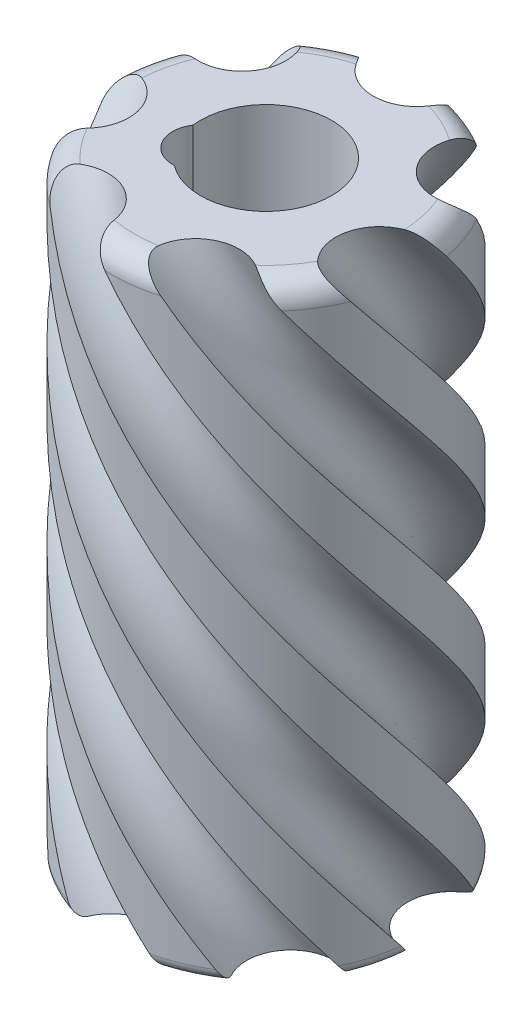
SolidWorks part; units mm, degrees
note: '?' marks a value the reader was unsure of.
ref_plane "Front Plane" through (0, 0, 0) normal (0, 0, 1) x (1, 0, 0)
ref_plane "Top Plane" through (0, 0, 0) normal (0, 1, 0) x (1, 0, 0)
ref_plane "Right Plane" through (0, 0, 0) normal (1, 0, 0) x (0, 0, -1)
sketch "Sketch4" plane through (0, 0, 0) normal (0, 1, 0) x (1, 0, 0)
  circle A0 centre (0, 0) radius 6.625
  dimension "D1" = 13.25
extrude "Boss-Extrude3" add sketch "Sketch4" along normal blind 26
sketch "Sketch2" plane through (0, 0, 0) normal (0, 1, 0) x (-1, 0, 0)
  circle A0 centre (0, 0) radius 2.8
  dimension "D1" = 5.6
fillet "Fillet1" radius 1 1 edges at (0, 26, 6.625)
sketch "Sketch3" plane through (0, 0, 0) normal (0, -1, 0) x (1, 0, 0)
  circle A0 centre (0, 0) radius 1.25
  dimension "D1" = 2.5
extrude "Cut-Extrude3" cut sketch "Sketch3" against normal blind 20
extrude "Cut-Extrude4" cut sketch "Sketch2" along normal blind 5.5
ref_axis "Axis2" through (0, 5.5, 0) along (0, -1, 0)?
sketch "Sketch30" plane through (0, 0, 0) normal (0, 1, 0) x (1, 0, 0)
  circle A0 centre (0, -0.0831) radius 3.9169
curve "Helix/Spiral2" pitch 52 height 26 turns 0.5
sketch "Sketch32" plane through (0, 0, 0) normal (0, 1, 0) x (1, 0, 0)
  circle A0 centre (0, -6.625) radius 1.875
  circle A2 centre (0, 0) radius 6.625 construction
  dimension "D1" = 3.75
sweep "Cut-Sweep3" cut profiles "Sketch32" path "Helix/Spiral2"
pattern_circular "CirPattern1" count 7 over 360 about axis through (0, 5.5, 0) along (0, -1, 0) of "Cut-Sweep3"
sketch "Sketch33" plane through (0, 26, 0) normal (0, 1, 0) x (1, 0, 0)
  circle A0 centre (0, 0) radius 2.8
  dimension "D1" = 5.6
extrude "Cut-Extrude5" cut sketch "Sketch33" against normal blind 5.5
fillet "Fillet3" radius 0.5 7 edges at (-2.8745, 0, 5.9689) (-6.4589, 0, 1.4742) (-5.1796, 0, -4.1306) (0, 0, -6.625) (5.1796, 0, -4.1306) (6.4589, 0, 1.4742) (2.8745, 0, 5.9689)
sketch "Sketch34" plane through (0, 5.5, 0) normal (0, -1, 0) x (1, 0, 0)
  line L1 (-1.1691, 2.025) -> (-2.3383, 0)
  line L2 (-2.3383, 0) -> (-1.1691, -2.025)
  line L3 (-1.1691, -2.025) -> (1.1691, -2.025)
  line L4 (1.1691, -2.025) -> (2.3383, 0)
  line L5 (2.3383, 0) -> (1.1691, 2.025)
  line L6 (1.1691, 2.025) -> (-1.1691, 2.025)
  circle A0 centre (0, 0) radius 2.025 construction
  dimension "D1" = 4.05
extrude "Cut-Extrude6" cut sketch "Sketch34" against normal blind 16
chamfer "Chamfer3" distance 0.7 angle 55 2 edges at (0, 5.5, 2.8) (0, 20.5, 2.8)
sketch "Sketch35" plane through (0, 26, 0) normal (0, 1, 0) x (1, 0, 0)
  circle A0 centre (-1.7537, -1.0125) radius 1.225
  point P4 (0, 0)
extrude "Cut-Extrude7" cut sketch "Sketch35" against normal blind 26
